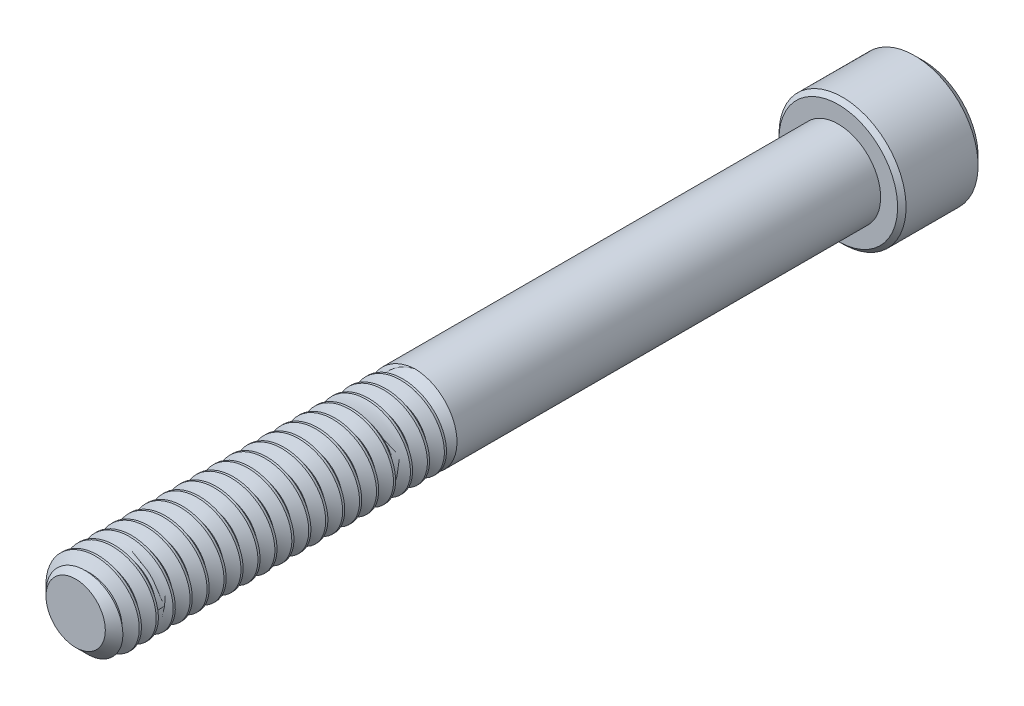
SolidWorks part; units mm, degrees
material "Alloy Steel"
ref_plane "Front Plane" through (0, 0, 0) normal (0, 0, 1) x (1, 0, 0)
ref_plane "Top Plane" through (0, 0, 0) normal (0, 1, 0) x (1, 0, 0)
ref_plane "Right Plane" through (0, 0, 0) normal (1, 0, 0) x (0, 0, -1)
sketch "Sketch1" plane through (0, 0, 0) normal (0, 0, 1) x (1, 0, 0)
  line L0 (0, 3.175) -> (0, -3.175) construction
  circle A0 centre (0, 0) radius 3.175
  dimension "OD" = 6.35
extrude "Extrude1" add sketch "Sketch1" against normal blind 57.15
sketch "Sketch2" plane through (0, 0, 0) normal (0, 0, 1) x (1, 0, 0)
  circle A0 centre (0, 0) radius 3.175 construction
  circle A1 centre (0, 0) radius 3.175
curve "Helix/Spiral1" pitch 1.27 height 27.94 turns 22 parameters "pitch"=1.27
chamfer "Chamfer3" distance 0.9525 angle 45 1 edges at (3.175, 0, 0)
sketch "Sketch3" plane through (0, 0, 0) normal (1, 0, 0) x (0, 0, -1)
  line L0 (-1.1112, 3.175) -> (-0.635, 2.3501)
  line L1 (-0.635, 2.3501) -> (-0.4763, 2.3501)
  line L2 (-0.4763, 2.3501) -> (0, 3.175)
  line L3 (-1.1112, 3.175) -> (0, 3.175)
  line L4 (-0.5556, 3.175) -> (-0.5556, 2.3501) construction
  line L5 (-0.8731, 2.7626) -> (-0.2381, 2.7626) construction
  line L6 (0, 3.175) -> (0, -3.175) construction
  dimension "D1" = 0.1588
  dimension "D2" = 0.635
  dimension "D3" = 60
sweep "Cut-Sweep1" cut profiles "Sketch3" path "Helix/Spiral1"
sketch "Sketch5" plane through (0, 0, 0) normal (1, 0, 0) x (0, 0, -1)
  line L1 (57.15, 3.175) -> (25.4, 3.175)
  line L2 (57.15, 3.175) -> (57.15, 0)
  line L3 (57.15, 0) -> (25.4, 0)
  line L4 (25.4, 3.175) -> (25.4, 0) construction
  line L6 (0, 0) -> (9.9695, 0) construction
  line L8 (25.4, 3.175) -> (22.225, 0)
  line L9 (22.225, 0) -> (25.4, 0)
  line L10 (57.15, -3.175) -> (57.15, 3.175) construction
  dimension "D1" = 45
  dimension "Thread min" = 25.4
revolve "partially thread" add sketch "Sketch5" angle 360 about L6
sketch "Sketch6" plane through (0, 0, -57.15) normal (0, 0, -1) x (-1, 0, 0)
  circle A0 centre (0, 0) radius 4.7625
  dimension "head dia" = 9.525
extrude "Extrude2" add sketch "Sketch6" along normal blind 6.35
sketch "Sketch7" plane through (0, 0, -63.5) normal (0, 0, -1) x (-1, 0, 0)
  line L1 (0, 2.7496) -> (-2.3812, 1.3748)
  line L2 (-2.3812, 1.3748) -> (-2.3813, -1.3748)
  line L3 (-2.3813, -1.3748) -> (0, -2.7496)
  line L4 (0, -2.7496) -> (2.3813, -1.3748)
  line L5 (2.3813, -1.3748) -> (2.3813, 1.3748)
  line L6 (2.3813, 1.3748) -> (0, 2.7496)
  circle A0 centre (0, 0) radius 2.3813 construction
  dimension "hex dia" = 4.7625
extrude "Cut-Extrude1" cut sketch "Sketch7" against normal blind 3.5719
sketch "Sketch8" plane through (0, 0, -63.5) normal (0, 0, -1) x (-1, 0, 0)
  circle A0 centre (0, 0) radius 2.7496
extrude "Cut-Extrude2" cut sketch "Sketch8" against normal blind 0.635 draft 45
chamfer "Chamfer1" distance 0.635 angle 45 1 edges at (-4.7625, 0, -63.5)
chamfer "Chamfer2" distance 0.3175 angle 45 1 edges at (-4.7625, 0, -57.15)
sketch "Sketch9" plane through (0, 0, 0) normal (1, 0, 0) x (0, 0, -1)
  line L0 (0, 3.175) -> (0, -3.175) construction
  line L1 (6.985, 3.175) -> (6.985, -3.175) construction
  line L2 (57.15, 4.7625) -> (57.15, -4.7625) construction
  line L3 (63.5, 4.7625) -> (63.5, -4.7625) construction
  line L4 (63.5, 0) -> (0, 0) construction
  line L5 (61.6852, 3.175) -> (61.6852, -3.175) construction
  dimension "D1" = 6.985
  dimension "D2" = 6.35
  dimension "D3" = 9.525
  dimension "D4" = 57.15
  dimension "Thread Length" = 61.6852
equation "\"D3@Helix/Spiral1\" = \"Thread min@Sketch5\"+(\"pitch@Helix/Spiral1\"*2)"
equation "\"D1@Sketch3\" = \"pitch@Helix/Spiral1\"*.125"
equation "\"D2@Sketch3\" = \"pitch@Helix/Spiral1\"*.5"
equation "\"D1@Cut-Extrude1\" = \"hex dia@Sketch7\"*.75"
equation "\"D1@Chamfer1\" = \"head depth@Extrude2\"/10"
equation "\"D1@Sketch9\" = \"pitch@Helix/Spiral1\"*5.5"
equation "\"D1@Chamfer2\" = \"D1@Chamfer1\"/2"
equation "\"D1@Cut-Extrude2\" = \"D1@Chamfer2\"*2"
equation "\"D1@Chamfer3\" = \"pitch@Helix/Spiral1\"*.750"
equation "\"D2@Sketch9\" = \"head depth@Extrude2\""
equation "\"D3@Sketch9\" = \"head dia@Sketch6\""
equation "\"D4@Sketch9\" = \"screw length@Extrude1\""
